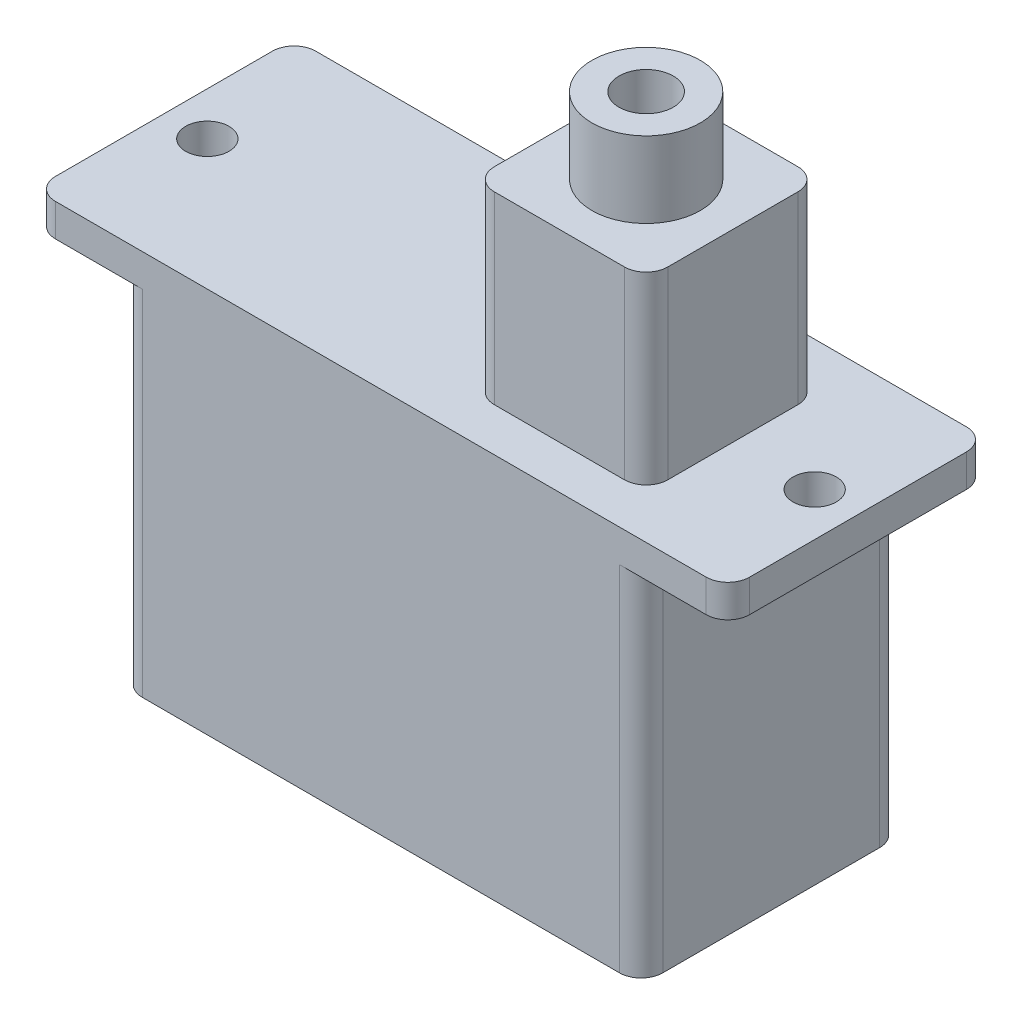
SolidWorks part; units mm, degrees
ref_plane "前视基准面" through (0, 0, 0) normal (0, 0, 1) x (1, 0, 0)
ref_plane "上视基准面" through (0, 0, 0) normal (0, 1, 0) x (1, 0, 0)
ref_plane "右视基准面" through (0, 0, 0) normal (1, 0, 0) x (0, 0, -1)
sketch "草图1" plane through (0, 0, 0) normal (0, 1, 0) x (1, 0, 0)
  line L1 (-12, 6) -> (12, 6)
  line L2 (-12, 6) -> (-12, -6)
  line L3 (-12, -6) -> (12, -6)
  line L4 (12, 6) -> (12, -6)
  line L5 (-12, 6) -> (12, -6) construction
  line L6 (-12, -6) -> (12, 6) construction
  point P0 (0, 0)
  dimension "D1" = 12
  dimension "D2" = 24
extrude "凸台-拉伸1" add sketch "草图1" along normal blind 16.3
sketch "草图2" plane through (0, 16.3, 0) normal (0, 1, 0) x (1, 0, 0)
  line L0 (-14, 0) -> (0, 0) construction
  line L1 (-16, 6) -> (16, 6)
  line L2 (-16, 6) -> (-16, -6)
  line L3 (-16, -6) -> (16, -6)
  line L4 (16, 6) -> (16, -6)
  line L5 (-16, 6) -> (16, -6) construction
  line L6 (-16, -6) -> (16, 6) construction
  line L7 (0, 0) -> (14, 0) construction
  line L8 (12, -6) -> (12, 6) construction
  line L9 (-12, 6) -> (12, 6)
  line L10 (-12, 6) -> (-12, -6)
  line L11 (-12, -6) -> (12, -6)
  line L12 (12, 6) -> (12, -6)
  line L13 (-12, 6) -> (12, -6) construction
  line L14 (-12, -6) -> (12, 6) construction
  line L16 (2.23, 4) -> (10.23, 4)
  line L17 (2.23, 4) -> (2.23, -4)
  line L18 (2.23, -4) -> (10.23, -4)
  line L19 (10.23, 4) -> (10.23, -4)
  line L20 (2.23, 4) -> (10.23, -4) construction
  line L21 (2.23, -4) -> (10.23, 4) construction
  circle A0 centre (14, 0) radius 1
  circle A1 centre (-14, 0) radius 1
  circle A2 centre (6.23, 0) radius 2.5
  circle A3 centre (6.23, 0) radius 1.25
  point P0 (0, 0)
  point P21 (12, 0)
  line M3 (12, -6) -> (12, 6)
  line M4 (12, 6) -> (-12, 6)
  line M5 (-12, 6) -> (-12, -6)
  line M6 (-12, -6) -> (12, -6)
  dimension "D5" = 2
  dimension "D6" = 2
  dimension "D7" = 5
  dimension "D8" = 2.5
  dimension "D1" = 32
  dimension "D2" = 12
  dimension "D3" = 14
  dimension "D4" = 14
  dimension "D9" = 5.77
  dimension "D10" = 8
  dimension "D11" = 8
extrude "凸台-拉伸3" add sketch "草图2" along normal blind 1.5 contours L16 L19 L18 L17 M6 M3 M4 M5 | L2 L3 L1 A1 M5 | L4 L1 L3 A0 M3 region at (-14, 16.3, -5.8735) region at (-1.78, 16.3, 0) region at (14, 16.3, -5.8735)
extrude "凸台-拉伸4" add sketch "草图2<4>" along normal blind 10 contours L19 L16 L17 L18 A2 | A2 A3 | A3 region at (6.23, 16.3, -3.8869) region at (3.8007, 16.3, 0) region at (6.23, 16.3, 0)
sketch "草图2<4>" plane through (0, 16.3, 0) normal (0, 1, 0) x (1, 0, 0) same geometry as "草图2"
extrude "凸台-拉伸5" add sketch "草图2<5>" along normal blind 13.5 contours A2 A3 region at (3.8007, 16.3, 0)
sketch "草图2<5>" plane through (0, 16.3, 0) normal (0, 1, 0) x (1, 0, 0) same geometry as "草图2"
fillet "圆角1" radius 1 4 edges at (16, 17.05, -6) (16, 17.05, 6) (-16, 17.05, -6) (-16, 17.05, 6)
fillet "圆角2" radius 1 4 edges at (10.23, 22.05, -4) (2.23, 22.05, -4) (2.23, 22.05, 4) (10.23, 22.05, 4)
fillet "圆角3" radius 1 4 edges at (-12, 8.15, -6) (-12, 8.15, 6) (12, 8.15, -6) (12, 8.15, 6)
